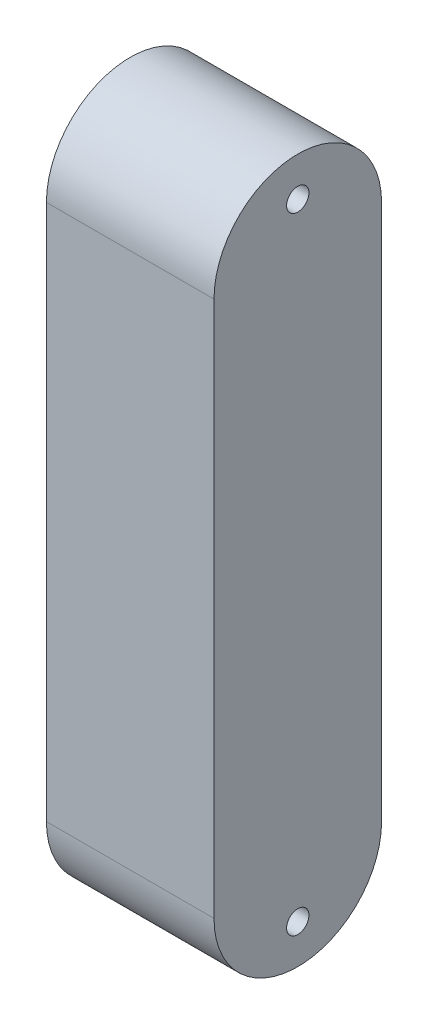
SolidWorks part; units mm, degrees
ref_plane "Front Plane" through (0, 0, 0) normal (0, 0, 1) x (1, 0, 0)
ref_plane "Top Plane" through (0, 0, 0) normal (0, 1, 0) x (1, 0, 0)
ref_plane "Right Plane" through (0, 0, 0) normal (1, 0, 0) x (0, 0, -1)
sketch "Sketch1" plane through (0, 0, 0) normal (0, 1, 0) x (1, 0, 0)
  line L1 (-7.5, 7.5) -> (7.5, 7.5)
  line L2 (-7.5, 7.5) -> (-7.5, -7.5)
  line L3 (-7.5, -7.5) -> (7.5, -7.5)
  line L4 (7.5, 7.5) -> (7.5, -7.5)
  dimension "D1" = 15
  dimension "D2" = 7.5
  dimension "D3" = 7.5
extrude "Boss-Extrude1" add sketch "Sketch1" along normal blind 63 contours L2 L3 L4 L1
sketch "Sketch3" plane through (7.5, 0, 0) normal (1, 0, 0) x (0, 0, -1)
  line L0 (7.5, 63) -> (-7.5, 63) construction
  line L1 (-7.5, 63) -> (-7.5, 0) construction
  line L2 (7.5, 0) -> (-7.5, 0) construction
  circle A0 centre (0, 59.5) radius 1
  circle A1 centre (0, 3.5) radius 1
  point P16 (-7.5, 55.2869)
  point P20 (7.5, 55.2863)
  dimension "D1" = 2
  dimension "D2" = 2
  dimension "D3" = 3.5
  dimension "D4" = 7.5
  dimension "D5" = 3.5
  dimension "D6" = 7.5
extrude "Cut-Extrude1" cut sketch "Sketch3" against normal blind 15
fillet "Fillet1" 2 edges at (0, 63, 7.5) (0, 63, -7.5) type full round first side face at (0, 31.5, 7.5) second side face at (0, 31.5, -7.5) middle face at (0, 63, 0)
fillet "Fillet2" 2 edges at (0, 0, -7.5) (0, 0, 7.5) type full round first side face at (0, 27.75, -7.5) second side face at (0, 27.75, 7.5) middle face at (0, 0, 0)
